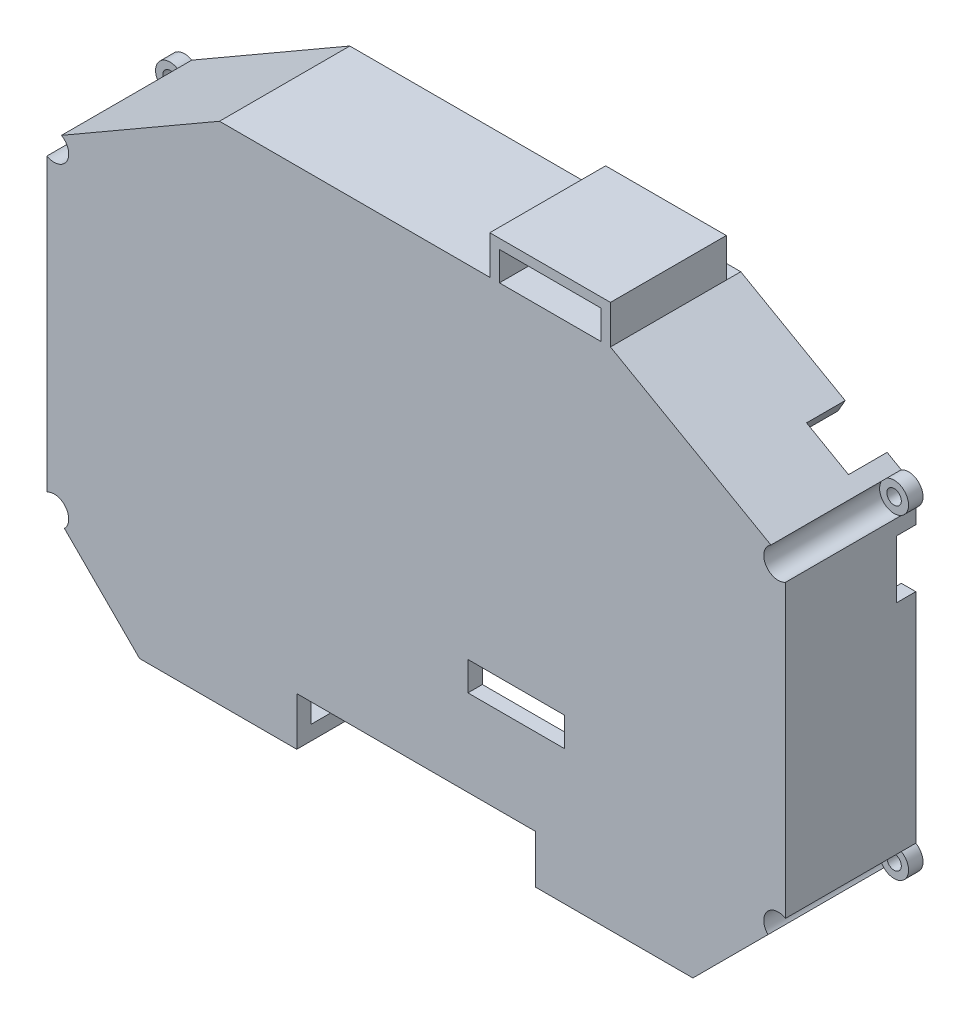
SolidWorks part; units mm, degrees
ref_plane "Front" through (0, 0, 0) normal (0, 0, 1) x (1, 0, 0)
ref_plane "Top" through (0, 0, 0) normal (0, 1, 0) x (1, 0, 0)
ref_plane "Right" through (0, 0, 0) normal (1, 0, 0) x (0, 0, -1)
sketch "草图2" plane through (0, 0, 0) normal (0, 0, 1) x (1, 0, 0)
  line L1 (73.4834, 35.3384) -> (40.2385, 54.25)
  line L2 (-76.5, 30.1519) -> (-76.5, -30.1519)
  line L4 (76.5, 30.1519) -> (76.5, -30.1519)
  line L5 (-75, 32.75) -> (75, -32.75) construction
  line L6 (-75, -32.75) -> (75, 32.75) construction
  line L7 (-40.7609, 54.25) -> (40.2385, 54.25)
  line L8 (75.75, 34.049) -> (75.7333, 34.0585)
  line L10 (-57.32, -50.43) -> (57.32, -50.43)
  line L11 (72.8787, -34.8713) -> (57.32, -50.43)
  line L12 (-72.8787, -34.8713) -> (-57.32, -50.43)
  line L13 (-73.5, 35.3481) -> (-40.7609, 54.25)
  circle A0 centre (-75, 32.75) radius 1.5
  circle A1 centre (75, 32.75) radius 1.5
  circle A2 centre (75, -32.75) radius 1.5
  circle A3 centre (-75, -32.75) radius 1.5
  arc A4 (-73.5, 35.3481) -> (-76.5, 30.1519) centre (-75, 32.75) ccw
  arc A5 (76.5, 30.1519) -> (73.4834, 35.3384) centre (75, 32.75) ccw
  arc A6 (72.8787, -34.8713) -> (76.5, -30.1519) centre (75, -32.75) ccw
  arc A7 (-76.5, -30.1519) -> (-72.8787, -34.8713) centre (-75, -32.75) ccw
  point P0 (0, 0)
extrude "凸台-拉伸1" add sketch "草图2" along normal blind 27 contours L2 A7 L12 L10 L11 A6 L4 A5 L1 L7 L13 A4 A0 A1 A2 A3 region at (-0.0184, 0.7527, 0)
shell "抽壳1" thickness 3 removed face at (-73.5, 32.75, 0)
sketch "草图3" plane through (0, 0, 27) normal (0, 0, 1) x (1, 0, 0)
  circle A0 centre (75, 32.75) radius 3
  circle A1 centre (75, -32.75) radius 3
  circle A2 centre (-75, -32.75) radius 3
  circle A3 centre (-75, 32.75) radius 3
extrude "切除-拉伸1" cut sketch "草图3" against normal blind 24
sketch "草图5" plane through (0, 0, 27) normal (0, 0, 1) x (1, 0, 0)
  line L1 (10.7074, -16.5771) -> (30.7074, -16.5771)
  line L2 (10.7074, -16.5771) -> (10.7074, -22.5771)
  line L3 (10.7074, -22.5771) -> (30.7074, -22.5771)
  line L4 (30.7074, -16.5771) -> (30.7074, -22.5771)
  line L5 (10.7074, -16.5771) -> (30.7074, -22.5771) construction
  line L6 (10.7074, -22.5771) -> (30.7074, -16.5771) construction
  point P0 (20.7074, -19.5771)
extrude "切除-拉伸3" cut sketch "草图5" against normal blind 32
sketch "草图6" plane through (76.5, 0, 0) normal (1, 0, 0) x (0, 0, -1)
  line L0 (0, 26.9774) -> (-4, 26.9774)
  line L1 (0, 30.1519) -> (0, -30.1519) construction
  line L2 (-4, 26.9774) -> (-4, 14.9774)
  line L3 (-4, 14.9774) -> (0, 14.9774)
  line L4 (0, 14.9774) -> (0, 26.9774)
extrude "切除-拉伸4" cut sketch "草图6" against normal blind 32
sketch "草图7" plane through (33.1533, 58.2805, 0) normal (0.4945, 0.8692, 0) x (0.8692, -0.4945, 0)
  line L0 (43.0325, 0) -> (43.0325, -8)
  line L1 (46.3989, 0) -> (8.1514, 0) construction
  line L2 (43.0325, -8) -> (33.0325, -8)
  line L3 (33.0325, -8) -> (33.0325, 0)
  line L4 (33.0325, 0) -> (43.0325, 0)
extrude "切除-拉伸5" cut sketch "草图7" against normal blind 32
sketch "草图8" plane through (0, 0, 27) normal (0, 0, 1) x (1, 0, 0)
  line L0 (40.2385, 54.25) -> (40.2385, 62.25)
  line L1 (40.2385, 62.25) -> (15.2385, 62.25)
  line L2 (15.2385, 62.25) -> (15.2385, 54.25)
  line L3 (-40.7609, 54.25) -> (40.2385, 54.25) construction
  line L4 (15.2385, 54.25) -> (17.2385, 54.25)
  line L5 (17.2385, 54.25) -> (17.2385, 60.25)
  line L6 (17.2385, 60.25) -> (38.2385, 60.25)
  line L7 (38.2385, 60.25) -> (38.2385, 54.25)
  line L8 (38.2385, 54.25) -> (40.2385, 54.25)
extrude "凸台-拉伸2" add sketch "草图8" against normal blind 24
sketch "草图9" plane through (0, 54.25, 0) normal (0, 1, 0) x (1, 0, 0)
  line L0 (22.7385, -3) -> (32.7385, -3)
  line L1 (-40.7609, 0) -> (40.2385, 0) construction
  line L3 (22.7385, -3) -> (22.7385, 0)
  line L4 (22.7385, 0) -> (32.7385, 0)
  line L5 (32.7385, -3) -> (32.7385, 0)
  line L6 (27.7385, -3) -> (32.7385, 0) construction
  line L7 (22.7385, 0) -> (27.7385, -3) construction
  point P4 (27.7385, -3)
extrude "切除-拉伸6" cut sketch "草图9" against normal blind 24
sketch "草图10" plane through (0, -50.43, 0) normal (0, -1, 0) x (1, 0, 0)
  circle A1 centre (-18.75, 20) radius 1.35
  circle A2 centre (18.75, 20) radius 1.35
extrude "切除-拉伸7" cut sketch "草图10" against normal blind 10
sketch "草图11" plane through (0, -50.43, 0) normal (0, -1, 0) x (1, 0, 0)
  line L1 (-57.32, 0) -> (57.32, 0) construction
  line L2 (0, 3) -> (2, 3)
  line L3 (2, 3) -> (2, 0)
  line L4 (2, 0) -> (-2, 0)
  line L5 (-2, 0) -> (-2, 3)
  line L6 (-2, 3) -> (0, 3)
extrude "切除-拉伸8" cut sketch "草图11" against normal blind 10
sketch "草图12" plane through (0, -50.43, 0) normal (0, -1, 0) x (1, 0, 0)
  line L2 (-24.75, 20) -> (-24.75, 27)
  line L4 (-57.32, 27) -> (57.32, 27) construction
  line L5 (-24.75, 27) -> (24.75, 27)
  line L6 (24.75, 20) -> (24.75, 0)
  line L7 (2, 0) -> (57.32, 0) construction
  line L8 (24.75, 0) -> (-24.75, 0)
  line L9 (-57.32, 0) -> (-2, 0) construction
  line L10 (-24.75, 0) -> (-24.75, 20)
  line L12 (24.75, 27) -> (24.75, 20)
extrude "切除-拉伸9" cut sketch "草图12" against normal blind 10
